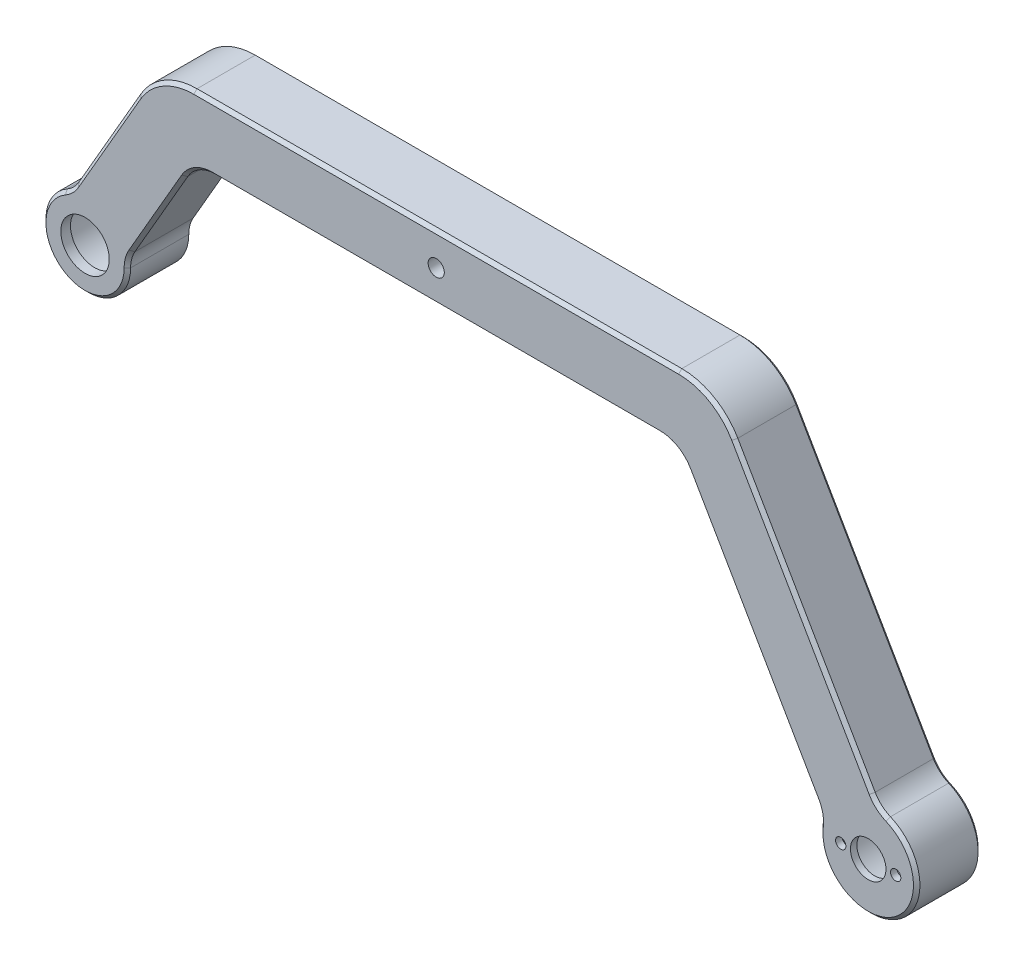
SolidWorks part; units mm, degrees
ref_plane "Front Plane" through (0, 0, 0) normal (0, 0, 1) x (1, 0, 0)
ref_plane "Top Plane" through (0, 0, 0) normal (0, 1, 0) x (1, 0, 0)
ref_plane "Right Plane" through (0, 0, 0) normal (1, 0, 0) x (0, 0, -1)
ref_axis "X" through (-88.99, 0, 0) along (1, 0, 0)
ref_axis "Y" through (0, 55, 0) along (0, -1, 0)
ref_axis "Z" through (0, 0, -88.99) along (0, 0, 1)
sketch "Sketch1" plane through (0, 0, 0) normal (0, 0, 1) x (1, 0, 0)
  line L0 (-75, -10) -> (75, -10)
  line L1 (-75, 10) -> (75, 10)
  line L3 (125, -96.6025) -> (75, -10)
  line L4 (-75, -10) -> (-100, -53.3013)
  line L5 (-117.3205, -43.3013) -> (-92.3205, 0)
  line L6 (92.3205, 0) -> (142.3205, -86.6025)
  line L7 (0, 10) -> (0, -10) construction
  arc A0 (142.3205, -86.6025) -> (125, -96.6025) centre (133.6603, -91.6025) cw
  arc A1 (-100, -53.3013) -> (-117.3205, -43.3013) centre (-108.6603, -48.3013) cw
  arc A2 (-92.3205, 0) -> (-75, 10) centre (-75, -10) cw
  arc A3 (75, 10) -> (92.3205, 0) centre (75, -10) cw
  circle A4 centre (0, 0) radius 2.5
  point P3 (0, 0)
  dimension "D1" = 150
  dimension "D7" = 5
  dimension "D2" = 20
  dimension "D3" = 100
  dimension "D4" = 50
  dimension "D5" = 60
  dimension "D6" = 60
extrude "Boss-Extrude1" add sketch "Sketch1" along normal mid plane 20
sketch "Sketch2" plane through (0, 0, 0) normal (0, 0, 1) x (1, 0, 0)
  line L0 (125.1603, -91.6025) -> (142.1603, -91.6025) construction
  circle A0 centre (-108.6603, -48.3013) radius 11.1
  circle A1 centre (-108.6603, -48.3013) radius 13.1
  circle A2 centre (-108.6603, -48.3013) radius 7.5
  circle A3 centre (133.6603, -91.6025) radius 13
  circle A4 centre (133.6603, -91.6025) radius 15
  circle A5 centre (133.6603, -91.6025) radius 5.5
  circle A6 centre (142.1603, -91.6025) radius 1.6
  circle A7 centre (125.1603, -91.6025) radius 1.6
  point P14 (133.6603, -91.6025)
  dimension "D1" = 22.2
  dimension "D3" = 15
  dimension "D4" = 26
  dimension "D6" = 11
  dimension "D7" = 3.2
  dimension "D8" = 17
  dimension "D2" = 2
  dimension "D5" = 2
extrude "Cut-Extrude1" cut sketch "Sketch2" against normal through all both and the other way through all contours A0 | A3
extrude "Boss-Extrude2" add sketch "Sketch2<3>" along normal up to surface (10 mm away) and the other way up to surface (10 mm away) contours A1 A0 region at (-121.3897, -48.3013, 0) up to face at (4.7306, -24.2929, 10) other way up to face at (4.7306, -24.2929, -10)
sketch "Sketch2<3>" plane through (0, 0, 0) normal (0, 0, 1) x (1, 0, 0) same geometry as "Sketch2"
extrude "Boss-Extrude3" add sketch "Sketch2<4>" against normal blind 3 from surface contours A0 A2 region at (-119.4463, -48.3013, 0) starting at face at (3.7028, -26.0731, 10)
sketch "Sketch2<4>" plane through (0, 0, 0) normal (0, 0, 1) x (1, 0, 0) same geometry as "Sketch2"
extrude "Boss-Extrude4" add sketch "Sketch2<5>" along normal up to surface (10 mm away) and the other way up to surface (10 mm away) contours A4 A3 region at (119.0845, -91.6025, 0) up to face at (3.7028, -26.0731, 10) other way up to face at (3.7028, -26.0731, -10)
sketch "Sketch2<5>" plane through (0, 0, 0) normal (0, 0, 1) x (1, 0, 0) same geometry as "Sketch2"
extrude "Boss-Extrude5" add sketch "Sketch2<6>" against normal blind 2 from surface contours A3 A7 A5 A6 region at (121.0279, -91.6025, 0) starting at face at (4.9591, -28.2491, 10)
sketch "Sketch2<6>" plane through (0, 0, 0) normal (0, 0, 1) x (1, 0, 0) same geometry as "Sketch2"
fillet "Fillet1" radius 10 6 edges at (136.7303, -76.9201, 0) (-113.0894, -35.9727, 0) (-95.7689, -45.9727, 0) (119.4098, -86.9201, 0) (75, -10, 0) (-75, -10, 0)
chamfer "Chamfer1" distance 1 angle 45 32 edges at (0, -10, -10) (74.2265, -11.3397, -10) (-74.2265, -11.3397, -10) (97.6934, -49.3061, -10) (-86.0536, -29.1455, -10) (118.6367, -86.6074, -10) (-95.2201, -45.7049, -10) (141.1603, -104.5929, -10) (-115.2103, -59.6462, -10) (136.8461, -76.0942, -10) (-113.1318, -35.3636, -10) (113.5705, -36.8061, -10) (-101.9308, -16.6455, -10) (85, 7.3205, -10) (-85, 7.3205, -10) (0, 10, -10) (0, -10, 10) (74.2265, -11.3397, 10) (-74.2265, -11.3397, 10) (97.6934, -49.3061, 10) (-86.0536, -29.1455, 10) (118.6367, -86.6074, 10) (-95.2201, -45.7049, 10) (141.1603, -104.5929, 10) (-115.2103, -59.6462, 10) (136.8461, -76.0942, 10) (-113.1318, -35.3636, 10) (113.5705, -36.8061, 10) (-101.9308, -16.6455, 10) (85, 7.3205, 10) (-85, 7.3205, 10) (0, 10, 10)
